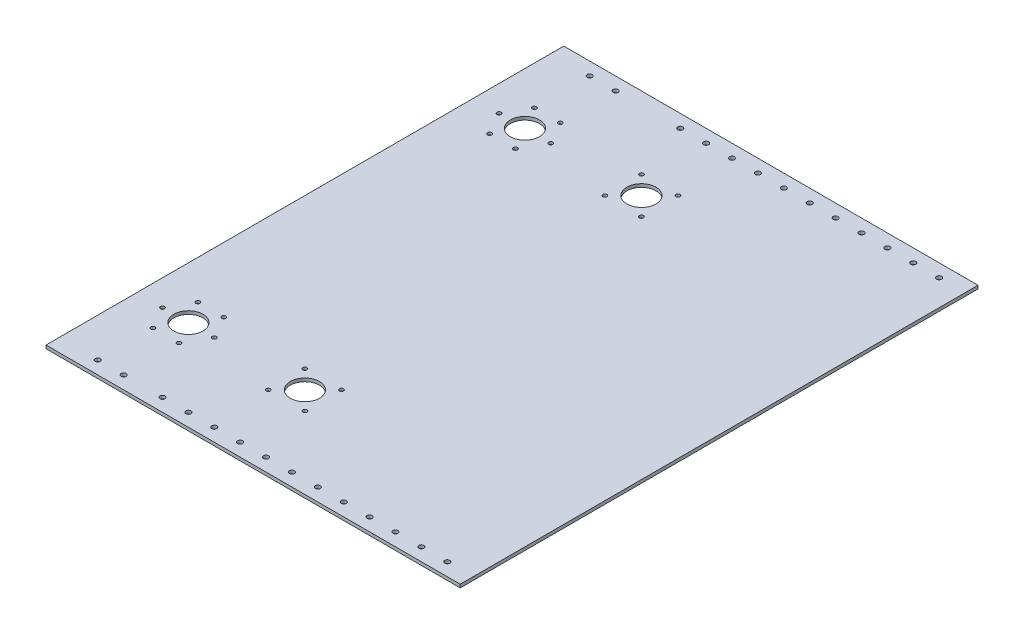
SolidWorks part; units mm, degrees
material "Lexan"
ref_plane "Front Plane" through (0, 0, 0) normal (0, 0, 1) x (1, 0, 0)
ref_plane "Top Plane" through (0, 0, 0) normal (0, 1, 0) x (1, 0, 0)
ref_plane "Right Plane" through (0, 0, 0) normal (1, 0, 0) x (0, 0, -1)
sketch "Sketch1" plane through (0, 0, 0) normal (0, 1, 0) x (1, 0, 0)
  line L1 (0, 0) -> (406.4, 0)
  line L2 (0, 0) -> (0, 508)
  line L3 (0, 508) -> (406.4, 508)
  line L4 (406.4, 0) -> (406.4, 508)
  dimension "D1" = 406.4
  dimension "D2" = 508
extrude "Boss-Extrude1" add sketch "Sketch1" along normal blind 3.175
sketch "Sketch2" plane through (0, 3.175, 0) normal (0, 1, 0) x (1, 0, 0)
  line L0 (107.95, 419.1) -> (107.95, 508) construction
  line L1 (50.8, 419.1) -> (165.1, 419.1) construction
  line L2 (406.4, 0) -> (406.4, 508) construction
  line L3 (50.8, 88.9) -> (165.1, 88.9) construction
  line L5 (406.4, 508) -> (0, 508) construction
  line L6 (107.95, 88.9) -> (107.95, 0) construction
  line L7 (0, 0) -> (406.4, 0) construction
  circle A0 centre (50.8, 419.1) radius 14.2875
  circle A1 centre (165.1, 419.1) radius 14.2875
  circle A2 centre (50.8, 88.9) radius 14.2875
  circle A3 centre (165.1, 88.9) radius 14.2875
  dimension "D1" = 28.575
  dimension "D2" = 28.575
  dimension "D3" = 28.575
  dimension "D4" = 28.575
  dimension "D5" = 114.3
  dimension "D6" = 114.3
  dimension "D7" = 330.2
  dimension "D9" = 241.3
extrude "Cut-Extrude1" cut sketch "Sketch2" against normal blind 3.175
sketch "Sketch3" plane through (0, 3.175, 0) normal (0, 1, 0) x (1, 0, 0)
  line L0 (0, 12.7) -> (406.4, 12.7) construction
  line L1 (0, 508) -> (0, 0) construction
  line L2 (406.4, 0) -> (406.4, 508) construction
  line L3 (0, 0) -> (406.4, 0) construction
  line L4 (101.6, 0) -> (101.6, 12.7) construction
  line L5 (0, 254) -> (406.4, 254) construction
  line L6 (101.6, 508) -> (101.6, 495.3) construction
  line L7 (0, 495.3) -> (406.4, 495.3) construction
  circle A0 centre (38.1, 12.7) radius 2.4892
  circle A1 centre (63.5, 12.7) radius 2.4892
  circle A2 centre (127, 12.7) radius 2.4892
  circle A3 centre (152.4, 12.7) radius 2.4892
  circle A4 centre (177.8, 12.7) radius 2.4892
  circle A5 centre (203.2, 12.7) radius 2.4892
  circle A6 centre (228.6, 12.7) radius 2.4892
  circle A7 centre (254, 12.7) radius 2.4892
  circle A8 centre (279.4, 12.7) radius 2.4892
  circle A9 centre (304.8, 12.7) radius 2.4892
  circle A10 centre (330.2, 12.7) radius 2.4892
  circle A11 centre (355.6, 12.7) radius 2.4892
  circle A12 centre (381, 12.7) radius 2.4892
  circle A13 centre (381, 495.3) radius 2.4892
  circle A14 centre (355.6, 495.3) radius 2.4892
  circle A15 centre (330.2, 495.3) radius 2.4892
  circle A16 centre (304.8, 495.3) radius 2.4892
  circle A17 centre (279.4, 495.3) radius 2.4892
  circle A18 centre (254, 495.3) radius 2.4892
  circle A19 centre (228.6, 495.3) radius 2.4892
  circle A20 centre (203.2, 495.3) radius 2.4892
  circle A21 centre (177.8, 495.3) radius 2.4892
  circle A22 centre (152.4, 495.3) radius 2.4892
  circle A23 centre (127, 495.3) radius 2.4892
  circle A24 centre (63.5, 495.3) radius 2.4892
  circle A25 centre (38.1, 495.3) radius 2.4892
  circle A27 centre (101.6, 12.7) radius 2.4892
  dimension "D1" = 4.9784
  dimension "D2" = 38.1
  dimension "D4" = 25.4
  dimension "D6" = 25.4
  dimension "D7" = 11
  dimension "D3" = 12.7
  dimension "D5" = 38.1
extrude "Cut-Extrude2" cut sketch "Sketch3" against normal through all both and the other way through all
sketch "Sketch4" plane through (0, 3.175, 0) normal (0, 1, 0) x (1, 0, 0)
  line L0 (25.4, 419.1) -> (38.1, 441.097) construction
  line L1 (38.1, 441.097) -> (63.5, 441.097) construction
  line L2 (63.5, 441.097) -> (76.2, 419.1) construction
  line L3 (76.2, 419.1) -> (63.5, 397.103) construction
  line L4 (63.5, 397.103) -> (38.1, 397.103) construction
  line L5 (38.1, 397.103) -> (25.4, 419.1) construction
  line L6 (0, 254) -> (406.4, 254) construction
  line L7 (183.0605, 401.1395) -> (147.1395, 401.1395) construction
  line L8 (183.0605, 401.1395) -> (183.0605, 437.0605) construction
  line L9 (183.0605, 437.0605) -> (147.1395, 437.0605) construction
  line L10 (147.1395, 401.1395) -> (147.1395, 437.0605) construction
  line L11 (183.0605, 401.1395) -> (147.1395, 437.0605) construction
  line L12 (183.0605, 437.0605) -> (147.1395, 401.1395) construction
  line L13 (0, 508) -> (0, 0) construction
  line L14 (406.4, 0) -> (406.4, 508) construction
  line L15 (183.0605, 70.9395) -> (147.1395, 106.8605) construction
  line L16 (183.0605, 106.8605) -> (147.1395, 70.9395) construction
  line L17 (147.1395, 106.8605) -> (147.1395, 70.9395) construction
  line L18 (183.0605, 70.9395) -> (147.1395, 70.9395) construction
  line L19 (183.0605, 106.8605) -> (183.0605, 70.9395) construction
  line L20 (183.0605, 106.8605) -> (147.1395, 106.8605) construction
  line L21 (38.1, 110.897) -> (25.4, 88.9) construction
  line L22 (63.5, 110.897) -> (38.1, 110.897) construction
  line L23 (76.2, 88.9) -> (63.5, 110.897) construction
  line L24 (63.5, 66.903) -> (76.2, 88.9) construction
  line L25 (38.1, 66.903) -> (63.5, 66.903) construction
  line L26 (25.4, 88.9) -> (38.1, 66.903) construction
  circle A0 centre (50.8, 419.1) radius 25.4 construction
  circle A1 centre (76.2, 419.1) radius 2.0193
  circle A2 centre (25.4, 419.1) radius 2.0193
  circle A3 centre (38.1, 441.097) radius 2.0193
  circle A4 centre (63.5, 441.097) radius 2.0193
  circle A5 centre (63.5, 397.103) radius 2.0193
  circle A6 centre (38.1, 397.103) radius 2.0193
  circle A7 centre (147.1395, 437.0605) radius 2.0193
  circle A8 centre (183.0605, 437.0605) radius 2.0193
  circle A9 centre (183.0605, 401.1395) radius 2.0193
  circle A10 centre (147.1395, 401.1395) radius 2.0193
  circle A11 centre (50.8, 88.9) radius 25.4 construction
  circle A12 centre (147.1395, 106.8605) radius 2.0193
  circle A13 centre (183.0605, 106.8605) radius 2.0193
  circle A14 centre (183.0605, 70.9395) radius 2.0193
  circle A15 centre (147.1395, 70.9395) radius 2.0193
  circle A16 centre (38.1, 110.897) radius 2.0193
  circle A17 centre (63.5, 110.897) radius 2.0193
  circle A18 centre (63.5, 66.903) radius 2.0193
  circle A19 centre (38.1, 66.903) radius 2.0193
  circle A20 centre (25.4, 88.9) radius 2.0193
  circle A21 centre (76.2, 88.9) radius 2.0193
  point P15 (165.1, 419.1)
  point P53 (165.1, 88.9)
  dimension "D1" = 50.8
  dimension "D2" = 4.0386
  dimension "D5" = 4.0386
  dimension "D3" = 35.921
  dimension "D4" = 35.921
extrude "Cut-Extrude3" cut sketch "Sketch4" against normal blind 2.54
